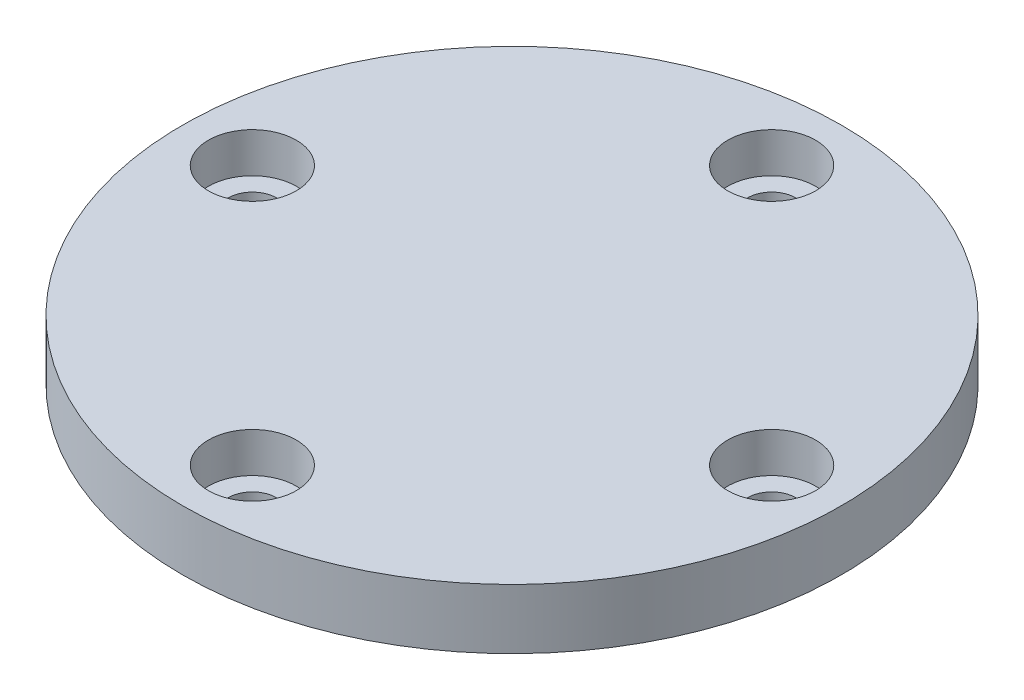
SolidWorks part; units mm, degrees
material "6061-T6 (SS)"
ref_plane "Front Plane" through (0, 0, 0) normal (0, 0, 1) x (1, 0, 0)
ref_plane "Top Plane" through (0, 0, 0) normal (0, 1, 0) x (1, 0, 0)
ref_plane "Right Plane" through (0, 0, 0) normal (1, 0, 0) x (0, 0, -1)
sketch "Sketch1" plane through (0, 0, 0) normal (0, 1, 0) x (1, 0, 0)
  circle A0 centre (0, 0) radius 16.5
  dimension "D1" = 33
extrude "Boss-Extrude1" add sketch "Sketch1" along normal blind 3
sketch "Sketch3" plane through (0, 3, 0) normal (0, 1, 0) x (1, 0, 0)
  circle A0 centre (0, -10.25) radius 0.25
  circle A1 centre (0, 0) radius 9.8
  dimension "D1" = 0.5
  dimension "D2" = 10.25
  dimension "D3" = 19.6
sketch "Sketch4" plane through (0, 3, 0) normal (0, -1, 0) x (1, 0, 0)
  line L0 (0, 0) -> (13.2597, 13.2597) construction
  circle A0 centre (7.7782, 7.7782) radius 1
  dimension "D2" = 2
  dimension "D1" = 11
sketch "Sketch5" plane through (0, 3, 0) normal (0, 1, 0) x (1, 0, 0)
  circle A0 centre (0, 0) radius 11
  dimension "D1" = 22
hole_wizard "CBORE for M2 SHCS1" positions "Sketch6" profile "Sketch7" counterbore size "M2" standard "ANSI Metric" end condition through all
sketch "Sketch6" plane through (0, 3, 0) normal (0, 1, 0) x (1, 0, 0)
  point P0 (13, 0)
  dimension "D1" = 13
sketch "Sketch7" plane through (13, 3, 0) normal (1, 0, 0) x (0, 0, 1)
  line L0 (0, 0) -> (0, 3)
  line L1 (0, 3) -> (1.2, 3)
  line L3 (1.2, 3) -> (1.2, 2)
  line L4 (1.2, 2) -> (2.2, 2)
  line L5 (2.2, 2) -> (2.2, 0)
  line L7 (2.2, 0) -> (0, 0)
  line L11 (0, -6.35) -> (0, 107.95) construction
  dimension "Thru Hole Dia." = 2.4
  dimension "Thru Hole Depth" = 3
  dimension "C'Bore Dia." = 4.4
  dimension "C'Bore Depth" = 2
pattern_circular "CirPattern1" count 4 over 360 about axis through (0, 3, 0) along (0, 1, 0) of "CBORE for M2 SHCS1"
sketch "Sketch8" plane through (0, 0, 0) normal (0, -1, 0) x (1, 0, 0)
  circle A0 centre (6, 0) radius 0.5
  dimension "D1" = 1
  dimension "D2" = 6
extrude "Cut-Extrude1" cut sketch "Sketch8" against normal blind 1.5
